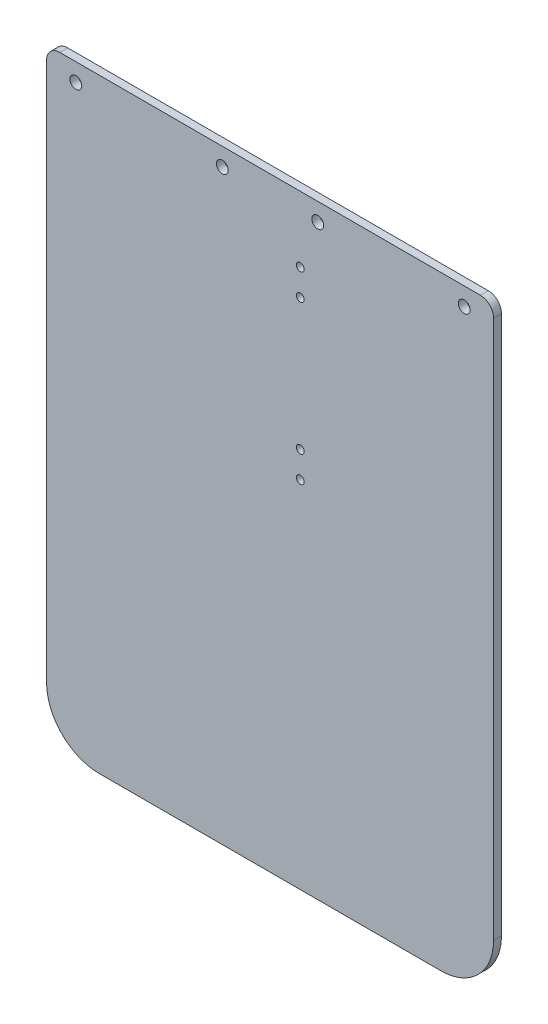
SolidWorks part; units mm, degrees
ref_plane "前视基准面" through (0, 0, 0) normal (0, 0, 1) x (1, 0, 0)
ref_plane "上视基准面" through (0, 0, 0) normal (0, 1, 0) x (1, 0, 0)
ref_plane "右视基准面" through (0, 0, 0) normal (1, 0, 0) x (0, 0, -1)
sketch "草图1" plane through (0, 0, 0) normal (0, 0, 1) x (1, 0, 0)
  line L1 (-85, 100) -> (85, 100)
  line L2 (-85, 100) -> (-85, -100)
  line L3 (-85, -100) -> (85, -100)
  line L4 (85, 100) -> (85, -100)
  line L5 (-85, 100) -> (85, -100) construction
  line L6 (-85, -100) -> (85, 100) construction
  point P0 (0, 0)
  dimension "D1" = 170
  dimension "D2" = 200
extrude "凸台-拉伸1" add sketch "草图1" along normal blind 3
sketch "草图2" plane through (0, 0, 0) normal (0, 0, -1) x (-1, 0, 0)
  circle A0 centre (-18.15, 93.15) radius 2.25 construction
  circle A1 centre (-73.85, 93.15) radius 2.25 construction
  circle A2 centre (18.15, 93.15) radius 2.25 construction
  circle A3 centre (73.85, 93.15) radius 2.25 construction
  circle A8 centre (-18.15, 93.15) radius 2.25
  circle A9 centre (-73.85, 93.15) radius 2.25
  circle A10 centre (18.15, 93.15) radius 2.25
  circle A11 centre (73.85, 93.15) radius 2.25
extrude "切除-拉伸1" cut sketch "草图2" against normal blind 10
sketch "草图4" plane through (0, 0, 0) normal (0, 0, -1) x (-1, 0, 0)
  line L1 (-85, -100) -> (85, -100)
  line L2 (-85, -100) -> (-85, -130)
  line L3 (-85, -130) -> (85, -130)
  line L4 (85, -100) -> (85, -130)
  dimension "D1" = 30
  dimension "D2" = 170
extrude "凸台-拉伸2" add sketch "草图4" against normal up to surface (3 mm away) up to face at (76.1, 93.15, 3)
fillet "圆角1" radius 20 2 edges at (85, -130, 1.5) (-85, -130, 1.5)
fillet "圆角2" radius 5 2 edges at (85, 100, 1.5) (-85, 100, 1.5)
sketch "草图6" plane through (0, 0, 3) normal (0, 0, 1) x (1, 0, 0)
  circle A0 centre (11.5, 5) radius 1.5
  circle A1 centre (11.5, 15) radius 1.5
  circle A2 centre (11.5, 65) radius 1.5
  circle A3 centre (11.5, 75) radius 1.5
  dimension "D1" = 3
  dimension "D2" = 3
  dimension "D3" = 3
  dimension "D4" = 3
extrude "切除-拉伸3" cut sketch "草图6" against normal through all
